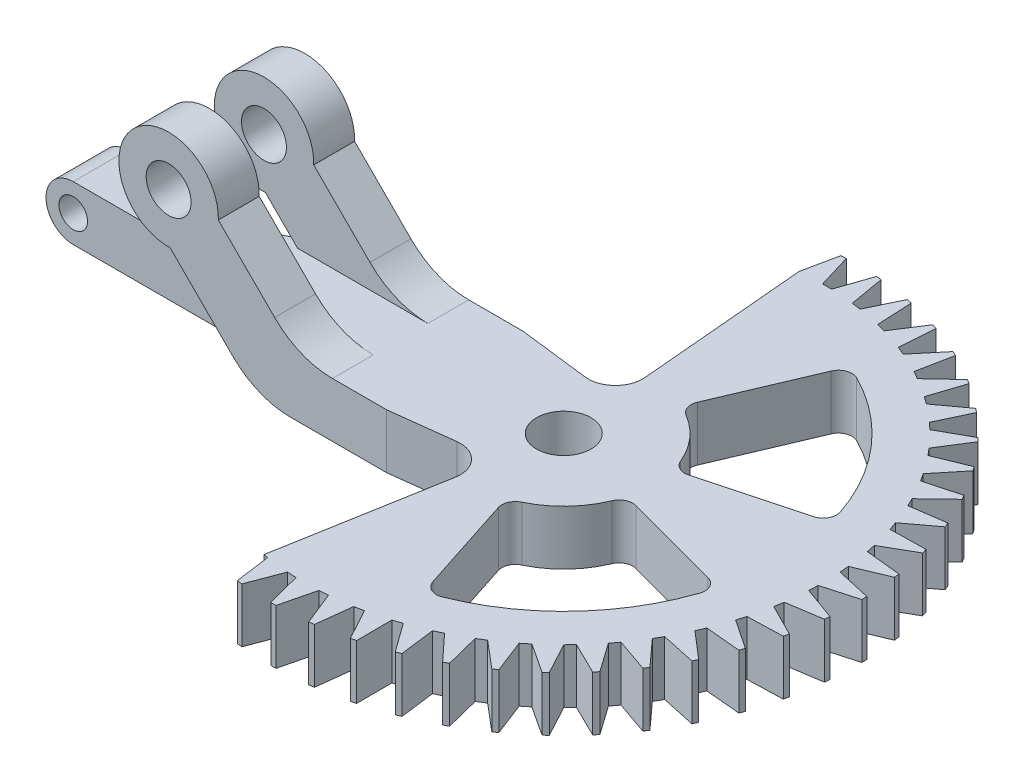
SolidWorks part; units mm, degrees
ref_plane "Front Plane" through (0, 0, 0) normal (0, 0, 1) x (1, 0, 0)
ref_plane "Top Plane" through (0, 0, 0) normal (0, 1, 0) x (1, 0, 0)
ref_plane "Right Plane" through (0, 0, 0) normal (1, 0, 0) x (0, 0, -1)
sketch "Sketch1" plane through (0, 0, 0) normal (0, 0, 1) x (1, 0, 0)
  line L0 (6.4645, -10) -> (16, -10)
  line L1 (16, -10) -> (16, -6)
  line L2 (16, -6) -> (9.5355, -6)
  line L3 (9.5355, -6) -> (3.6483, -0.1127)
  line L4 (6.4645, -10) -> (0.1127, -3.6483)
  line L5 (0, 0) -> (14.0151, -14.0151) construction
  line L6 (0, 0) -> (0, -20.1214) construction
  circle A0 centre (0, 0) radius 1.65
  arc A1 (3.6483, -0.1127) -> (0.1127, -3.6483) centre (0, 0) ccw
  arc A2 (2.5809, -2.5809) -> (3.6483, -0.1127) centre (0, 0) ccw construction
  arc A3 (0.1127, -3.6483) -> (2.5809, -2.5809) centre (0, 0) ccw construction
  circle A4 centre (0, 0) radius 3.65 construction
  point P5 (4, 0)
  dimension "D1" = 3.3
  dimension "D3" = 4
  dimension "D4" = 5
  dimension "D5" = 16
  dimension "D6" = 6
  dimension "D7" = 45
  dimension "D2" = 2
extrude "Boss-Extrude1" add sketch "Sketch1" along normal mid plane 10
sketch "Sketch3" plane through (0, -10, 0) normal (0, -1, 0) x (1, 0, 0)
  line L0 (-3.65, -5) -> (3.65, -5) construction
  line L1 (3.65, 5) -> (-3.65, 5) construction
  line L4 (6.4645, -5) -> (6.4645, 5) construction
  line L6 (-3.65, -5) -> (3.65, -5) construction
  line L7 (3.65, 5) -> (-3.65, 5) construction
  line L8 (6.4645, 2) -> (-3.65, 2)
  line L9 (-3.65, 2) -> (-3.65, -2)
  line L10 (6.4645, -2) -> (6.4645, 2)
  line L11 (-3.65, -2) -> (6.4645, -2)
  line L12 (0, 0) -> (-8.9484, 0) construction
  line L13 (6.4645, 2) -> (6.4645, 5) construction
  line L14 (6.4645, -5) -> (6.4645, -2) construction
  dimension "D1" = 4
extrude "Cut-Extrude1" cut sketch "Sketch3" against normal through all
sketch "Sketch4" plane through (0, -10, 0) normal (0, -1, 0) x (1, 0, 0)
  line L0 (16, 5) -> (16, -5) construction
  line L1 (16, 5) -> (16, -5)
  line L2 (0, 0) -> (22, 0) construction
  line L4 (16, -5) -> (21.1955, -4.3696)
  line L5 (24, -40.1964) -> (24, 25.6785) construction
  line L8 (20, 0) -> (22, 0) construction
  line L9 (24, 0) -> (21.8146, -24.9797) construction
  line L10 (23.4288, -6.5294) -> (22.1262, -21.4182)
  line L12 (26, 0) -> (28, 0) construction
  line L13 (22, 0) -> (24, 0) construction
  line L14 (24, -4.0293) -> (24.4818, -3.9709) construction
  line L15 (23.6437, -4.0726) -> (24, -4.0293) construction
  line L16 (24, 0) -> (26, 0) construction
  line L17 (16, 5) -> (20.5948, 4.4425)
  line L18 (23.4288, 6.5294) -> (22.1262, 21.4182) construction
  line L20 (16, 0) -> (20, 0) construction
  line L21 (26, 0) -> (53.2333, 0) construction
  line L22 (24, 0) -> (26, 0) construction
  line L23 (22, 0) -> (24, 0) construction
  line L25 (21.1955, 4.3696) -> (23.274, 4.1174) construction
  line L26 (20.2666, 21.1734) -> (22.8053, 6.7752)
  line L28 (20.5948, 4.4425) -> (21.1955, 4.3696) construction
  line L29 (23.274, 4.1174) -> (23.3054, 3.9392) construction
  line L33 (24, 0) -> (19.5917, 25.0008) construction
  line L34 (23.0803, 5.216) -> (23.274, 4.1174) construction
  line L35 (22.8053, 6.7752) -> (23.0803, 5.216) construction
  line L37 (23.274, 4.1174) -> (24, 4.0293) construction
  circle A0 centre (24, 0) radius 2
  arc A1 (24.4818, -3.9709) -> (28, 0) centre (24, 0) ccw construction
  arc A2 (20, 0) -> (24.4818, -3.9709) centre (24, 0) ccw construction
  circle A3 centre (24, 0) radius 4 construction
  circle A4 centre (24, 0) radius 4 construction
  arc A5 (22.1262, -21.4182) -> (20.2666, 21.1734) centre (24, 0) ccw
  arc A8 (24.4818, -3.9709) -> (20, 0) centre (24, 0) ccw construction
  arc A12 (23.4288, -6.5294) -> (21.1955, -4.3696) centre (21.4364, -6.3551) ccw
  arc A14 (24, 2) -> (22, 0) centre (24, 0) ccw construction
  arc A15 (26, 0) -> (24, 2) centre (24, 0) ccw construction
  circle A16 centre (24, 0) radius 2 construction
  arc A17 (23.4288, 6.5294) -> (21.1955, 4.3696) centre (21.4364, 6.3551) cw construction
  circle A19 centre (24, 0) radius 21.5 construction
  arc A20 (20.5948, 4.4425) -> (22.8053, 6.7752) centre (20.8357, 6.4279) ccw
  arc A21 (22.8053, 6.7752) -> (20.5948, 4.4425) centre (20.8357, 6.4279) ccw construction
  point P10 (28, 0)
  point P16 (25.9126, 0.5847)
  dimension "D1" = 4
  dimension "D4" = 43
  dimension "D10" = 24
  dimension "D5" = 4
  dimension "D6" = 2
  dimension "D2" = 10
  dimension "D7" = 5
  dimension "D3" = 2
extrude "Boss-Extrude2" add sketch "Sketch4" against normal up to surface (4 mm away) up to face at (12.7678, -6, 0)
sketch "Sketch5" plane through (0, 0, 0) normal (0, 0, 1) x (1, 0, 0)
  line L2 (6.4645, -10) -> (-10, -10)
  line L3 (9.5355, -6) -> (-10, -6)
  line L4 (16, -6) -> (9.5355, -6) construction
  line L5 (16, -6) -> (9.5355, -6)
  line L6 (6.4645, -10) -> (16, -10) construction
  line L7 (6.4645, -10) -> (16, -10)
  line L8 (16, -10) -> (16, -6)
  arc A2 (-10, -6) -> (-10, -10) centre (-10, -8) ccw
  circle A3 centre (-10, -8) radius 1.05
  arc A4 (-10, -10) -> (-10, -6) centre (-10, -8) ccw construction
  dimension "D2" = 2.1
  dimension "D1" = 10
extrude "Boss-Extrude3" add sketch "Sketch5" along normal mid plane 4
sketch "Sketch7" plane through (0, -10, 0) normal (0, -1, 0) x (1, 0, 0)
  line L0 (23.4288, -6.5294) -> (22.1262, -21.4182) construction
  line L1 (23.4288, -6.5294) -> (22.344, -18.9277) construction
  line L2 (24, 0) -> (19.8793, -26.0172) construction
  line L3 (24, 0) -> (22.5091, -28.4487) construction
  line L4 (24, 0) -> (21.6845, -18.8584) construction
  line L5 (22.344, -18.9277) -> (22.1262, -21.4182) construction
  line L6 (20.6367, -21.2353) -> (21.6845, -18.8584)
  line L7 (22.8748, -21.4705) -> (22.344, -18.9277)
  arc A0 (21.6845, -18.8584) -> (22.344, -18.9277) centre (24, 0) ccw
  arc A1 (22.1262, -21.4182) -> (20.2666, 21.1734) centre (24, 0) ccw construction
  arc A2 (20.6367, -21.2353) -> (22.8748, -21.4705) centre (24, 0) ccw
  arc A3 (22.8748, -21.4705) -> (20.2666, 21.1734) centre (24, 0) ccw construction
  arc A4 (23.0056, -18.974) -> (21.0277, -18.7661) centre (24, 0) ccw construction
  arc A5 (21.0277, -18.7661) -> (21.6845, -18.8584) centre (24, 0) ccw construction
  arc A6 (22.344, -18.9277) -> (23.0056, -18.974) centre (24, 0) ccw construction
  dimension "D1" = 2.5
  dimension "D2" = 4
  dimension "D3" = 2
  dimension "D4" = 2
extrude "Cut-Extrude3" cut sketch "Sketch7" against normal up to next
pattern_circular "CirPattern2" count 29 every 7 about axis through (24, 0, 0) along (0, 1, 0) of "Cut-Extrude3"
sketch "Sketch8" plane through (0, -6, 0) normal (0, 1, 0) x (1, 0, 0)
  line L0 (22.8053, -6.7752) -> (20.7007, -18.7113) construction
  line L1 (22.344, 18.9277) -> (23.4288, 6.5294) construction
  line L2 (21.2216, -15.7569) -> (20.7007, -18.7113) construction
  line L3 (22.344, 18.9277) -> (22.6055, 15.9391) construction
  line L4 (26.561, 6.0333) -> (30.2517, 14.7281)
  line L5 (28.9443, -15.2169) -> (26.0254, -6.2335)
  line L6 (24, 0) -> (52.5082, 0) construction
  line L7 (30.331, -1.6964) -> (39.4548, -4.1411)
  line L8 (30.331, 1.6964) -> (39.4548, 4.1411)
  line L9 (22.6055, 15.9391) -> (23.4288, 6.5294) construction
  line L10 (22.8619, -6.4547) -> (21.2216, -15.7569) construction
  circle A0 centre (24, 0) radius 2 construction
  circle A1 centre (24, 0) radius 2 construction
  arc A2 (26.0254, -6.2335) -> (30.331, -1.6964) centre (24, 0) ccw
  arc A3 (28.9443, -15.2169) -> (39.4548, -4.1411) centre (24, 0) ccw
  arc A4 (30.2517, 14.7281) -> (22.6055, 15.9391) centre (24, 0) ccw construction
  arc A5 (26.561, 6.0333) -> (23.4288, 6.5294) centre (24, 0) ccw construction
  arc A6 (30.331, 1.6964) -> (26.561, 6.0333) centre (24, 0) ccw
  arc A7 (30.5543, 0) -> (30.331, 1.6964) centre (24, 0) ccw construction
  arc A8 (39.4548, 4.1411) -> (30.2517, 14.7281) centre (24, 0) ccw
  arc A9 (40, 0) -> (39.4548, 4.1411) centre (24, 0) ccw construction
  arc A10 (39.4548, -4.1411) -> (40, 0) centre (24, 0) ccw construction
  arc A11 (30.331, -1.6964) -> (30.5543, 0) centre (24, 0) ccw construction
  arc A12 (22.8619, -6.4547) -> (26.0254, -6.2335) centre (24, 0) ccw construction
  arc A13 (21.2216, -15.7569) -> (28.9443, -15.2169) centre (24, 0) ccw construction
  dimension "D4" = 16
  dimension "D1" = 28
  dimension "D2" = 28
  dimension "D3" = 30
extrude "Cut-Extrude4" cut sketch "Sketch8" against normal up to next
fillet "Fillet3" radius 1 8 edges at (39.4548, -8, 4.1411) (28.9443, -8, 15.2169) (30.331, -8, -1.6964) (26.561, -8, -6.0333) (26.0254, -8, 6.2335) (30.331, -8, 1.6964) (30.2517, -8, -14.7281) (39.4548, -8, -4.1411)
sketch "Sketch9" plane through (0, -6, 0) normal (0, 1, 0) x (1, 0, 0)
  line L0 (6.4645, -2) -> (6.4645, 2) construction
  line L1 (6.4645, -2) -> (6.4645, 2)
  line L2 (6.4645, 2) -> (11.4645, 2)
  line L3 (11.4645, 2) -> (11.4645, -2)
  line L4 (11.4645, -2) -> (6.4645, -2)
  dimension "D1" = 5
extrude "Cut-Extrude6" cut sketch "Sketch9" along normal through all
fillet "Fillet4" radius 6 4 edges at (6.4645, -10, 3.5) (6.4645, -10, -3.5) (9.5355, -6, 3.5) (9.5355, -6, -3.5)
fillet "Fillet5" radius 2 4 edges at (6.6536, -9.5433, 2) (6.6536, -9.5433, -2) (3.5858, -7.1213, 2) (3.5858, -7.1213, -2)
